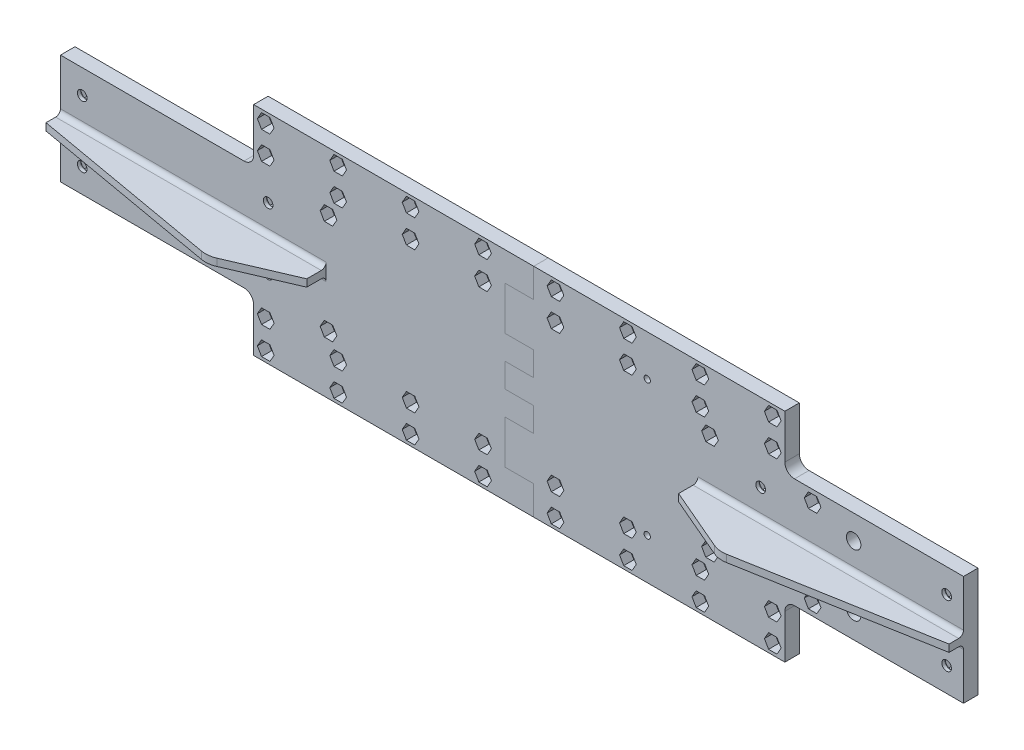
SolidWorks part; units mm, degrees
ref_plane "Top Plane" through (0, 0, 0) normal (0, 0, 1) x (1, 0, 0)
ref_plane "Right Plane" through (0, 0, 0) normal (0, 1, 0) x (1, 0, 0)
ref_plane "Front Plane" through (0, 0, 0) normal (1, 0, 0) x (0, 0, -1)
sketch "Sketch1" plane through (0, 0, 0) normal (0, 0, 1) x (1, 0, 0)
  line L0 (-187, 81) -> (187, -81) construction
  line L1 (-187, 81) -> (187, 81) construction
  line L2 (-187, 81) -> (-187, -81) construction
  line L3 (-187, -81) -> (187, -81) construction
  line L4 (187, 81) -> (187, -81) construction
  line L5 (-187, -22.75) -> (-107, -22.75) construction
  line L6 (-107, -22.75) -> (-107, -81) construction
  line L7 (113, -81) -> (113, -22.75) construction
  line L8 (113, -22.75) -> (187, -22.75) construction
  line L9 (-187, 0) -> (187, 0) construction
  line L10 (113, 22.75) -> (187, 22.75) construction
  line L11 (113, 81) -> (113, 22.75) construction
  line L12 (-107, 22.75) -> (-107, 81) construction
  line L13 (-187, 22.75) -> (-107, 22.75) construction
  line L14 (85.2, -81) -> (85.2, 81) construction
  line L15 (-93, -81) -> (-93, 81) construction
  line L16 (-187, -2.75) -> (187, -2.75) construction
  line L17 (187, 2.75) -> (-187, 2.75) construction
  text T0 "FRONT" font "Century Gothic" height in points 80
  dimension "D1" = 374
  dimension "D2" = 162
  dimension "D3" = 45.5
  dimension "D4" = 80
  dimension "D5" = 74
  dimension "D6" = 27.8
  dimension "D7" = 14
  dimension "D8" = 20
  dimension "D9" = 20
sketch "Sketch2" plane through (0, 0, 0) normal (0, 0, 1) x (1, 0, 0)
  line L0 (-187, 81) -> (-187, -81) construction
  line L1 (-187, 81) -> (187, 81) construction
  line L2 (187, 81) -> (187, -81) construction
  line L3 (-187, -81) -> (187, -81) construction
  line L4 (113, -81) -> (113, -22.75) construction
  line L5 (113, -22.75) -> (187, -22.75) construction
  line L6 (113, 22.75) -> (187, 22.75) construction
  line L7 (113, 81) -> (113, 22.75) construction
  line L8 (-107, 22.75) -> (-107, 81) construction
  line L9 (-187, 22.75) -> (-107, 22.75) construction
  line L10 (-107, -22.75) -> (-107, -81) construction
  line L11 (-187, -22.75) -> (-107, -22.75) construction
  line L12 (-187, 22.75) -> (-187, -22.75)
  line L13 (-107, 81) -> (113, 81)
  line L14 (187, 22.75) -> (187, -22.75)
  line L15 (-107, -81) -> (113, -81)
  line L16 (113, -81) -> (113, -22.75)
  line L17 (113, -22.75) -> (187, -22.75)
  line L18 (113, 22.75) -> (187, 22.75)
  line L19 (113, 81) -> (113, 22.75)
  line L20 (-107, 22.75) -> (-107, 81)
  line L21 (-187, 22.75) -> (-107, 22.75)
  line L22 (-107, -22.75) -> (-107, -81)
  line L23 (-187, -22.75) -> (-107, -22.75)
extrude "Boss-Extrude1" add sketch "Sketch2" along normal mid plane 6
sketch "Sketch5" plane through (0, 0, -3) normal (0, 0, -1) x (-1, 0, 0)
  line L0 (0, 81) -> (0, -81) construction
  line L1 (187, 81) -> (-187, 81) construction
  line L2 (187, -81) -> (-187, -81) construction
  line L4 (-180, 0) -> (178, 0) construction
  line L5 (-180, 12.75) -> (-103, 12.75) construction
  line L6 (-180, 12.75) -> (-180, -12.75) construction
  line L7 (-180, -12.75) -> (-103, -12.75) construction
  line L8 (-103, 12.75) -> (-103, -12.75) construction
  line L9 (101, 12.75) -> (178, 12.75) construction
  line L10 (101, 12.75) -> (101, -12.75) construction
  line L11 (101, -12.75) -> (178, -12.75) construction
  line L12 (178, 12.75) -> (178, -12.75) construction
  circle A8 centre (-103, -12.75) radius 2
  circle A9 centre (-103, 12.75) radius 2
  circle A10 centre (-180, 12.75) radius 2
  circle A11 centre (-180, -12.75) radius 2
  circle A12 centre (178, 12.75) radius 2
  circle A13 centre (178, -12.75) radius 2
  circle A14 centre (101, -12.75) radius 2
  circle A15 centre (101, 12.75) radius 2
  dimension "D3" = 25.5
  dimension "D6" = 4
  dimension "D1" = 77
  dimension "D2" = 103
  dimension "D4" = 101
  dimension "D5" = 77
extrude "Cut-Extrude2" cut sketch "Sketch5" against normal up to next
sketch "Sketch9" plane through (0, 0, 3) normal (0, 0, 1) x (1, 0, 0)
  line L0 (-107.9535, -35) -> (101.269, -35) construction
  line L1 (-12, -40.75) -> (18, -40.75) construction
  line L2 (-12, -29.25) -> (-42, -29.25) construction
  line L3 (-12, -29.25) -> (18, -29.25) construction
  line L4 (-194.5845, 0) -> (205.1662, 0) construction
  line L5 (3, -85.4344) -> (3, 85.4344) construction
  line L6 (-12, -40.75) -> (-42, -40.75) construction
  line L7 (-107, 81) -> (113, -81) construction
  line L8 (-40.2679, -37.75) -> (-43.7321, -37.75) construction
  line L9 (-13.7321, -37.75) -> (-15.4641, -40.75) construction
  line L10 (-15.4641, -40.75) -> (-13.7321, -43.75) construction
  line L11 (-13.7321, -43.75) -> (-10.2679, -43.75) construction
  line L12 (-10.2679, -43.75) -> (-8.5359, -40.75) construction
  line L13 (-8.5359, -40.75) -> (-10.2679, -37.75) construction
  line L14 (-10.2679, -37.75) -> (-13.7321, -37.75) construction
  line L15 (-43.7321, -37.75) -> (-45.4641, -40.75) construction
  line L16 (-45.4641, -40.75) -> (-43.7321, -43.75) construction
  line L17 (-43.7321, -43.75) -> (-40.2679, -43.75) construction
  line L18 (-40.2679, -43.75) -> (-38.5359, -40.75) construction
  line L19 (-38.5359, -40.75) -> (-40.2679, -37.75) construction
  line L20 (-70.2679, -37.75) -> (-73.7321, -37.75) construction
  line L21 (-73.7321, -37.75) -> (-75.4641, -40.75) construction
  line L22 (-75.4641, -40.75) -> (-73.7321, -43.75) construction
  line L23 (-73.7321, -43.75) -> (-70.2679, -43.75) construction
  line L24 (-70.2679, -43.75) -> (-68.5359, -40.75) construction
  line L25 (-68.5359, -40.75) -> (-70.2679, -37.75) construction
  line L26 (-100.2679, -37.75) -> (-103.7321, -37.75) construction
  line L27 (-103.7321, -37.75) -> (-105.4641, -40.75) construction
  line L28 (-105.4641, -40.75) -> (-103.7321, -43.75) construction
  line L29 (-103.7321, -43.75) -> (-100.2679, -43.75) construction
  line L30 (-100.2679, -43.75) -> (-98.5359, -40.75) construction
  line L31 (-98.5359, -40.75) -> (-100.2679, -37.75) construction
  line L32 (-43.7321, -37.75) -> (-40.2679, -43.75) construction
  line L33 (-42, -40.75) -> (-12, -40.75) construction
  line L34 (-8.5359, -29.25) -> (-10.2679, -32.25) construction
  line L35 (-10.2679, -26.25) -> (-8.5359, -29.25) construction
  line L36 (-13.7321, -26.25) -> (-10.2679, -26.25) construction
  line L37 (-15.4641, -29.25) -> (-13.7321, -26.25) construction
  line L38 (-13.7321, -32.25) -> (-15.4641, -29.25) construction
  line L39 (-10.2679, -32.25) -> (-13.7321, -32.25) construction
  line L40 (-43.7321, -26.25) -> (-40.2679, -26.25) construction
  line L41 (-45.4641, -29.25) -> (-43.7321, -26.25) construction
  line L42 (-43.7321, -32.25) -> (-45.4641, -29.25) construction
  line L43 (-40.2679, -32.25) -> (-43.7321, -32.25) construction
  line L44 (-38.5359, -29.25) -> (-40.2679, -32.25) construction
  line L45 (-40.2679, -26.25) -> (-38.5359, -29.25) construction
  line L46 (-73.7321, -26.25) -> (-70.2679, -26.25) construction
  line L47 (-75.4641, -29.25) -> (-73.7321, -26.25) construction
  line L48 (-73.7321, -32.25) -> (-75.4641, -29.25) construction
  line L49 (-70.2679, -32.25) -> (-73.7321, -32.25) construction
  line L50 (-68.5359, -29.25) -> (-70.2679, -32.25) construction
  line L51 (-70.2679, -26.25) -> (-68.5359, -29.25) construction
  line L52 (-103.7321, -26.25) -> (-100.2679, -26.25) construction
  line L53 (-105.4641, -29.25) -> (-103.7321, -26.25) construction
  line L54 (-103.7321, -32.25) -> (-105.4641, -29.25) construction
  line L55 (-100.2679, -32.25) -> (-103.7321, -32.25) construction
  line L56 (-98.5359, -29.25) -> (-100.2679, -32.25) construction
  line L57 (-100.2679, -26.25) -> (-98.5359, -29.25) construction
  line L58 (106.2679, -26.25) -> (104.5359, -29.25) construction
  line L59 (104.5359, -29.25) -> (106.2679, -32.25) construction
  line L60 (106.2679, -32.25) -> (109.7321, -32.25) construction
  line L61 (109.7321, -32.25) -> (111.4641, -29.25) construction
  line L62 (111.4641, -29.25) -> (109.7321, -26.25) construction
  line L63 (109.7321, -26.25) -> (106.2679, -26.25) construction
  line L64 (76.2679, -26.25) -> (74.5359, -29.25) construction
  line L65 (74.5359, -29.25) -> (76.2679, -32.25) construction
  line L66 (76.2679, -32.25) -> (79.7321, -32.25) construction
  line L67 (79.7321, -32.25) -> (81.4641, -29.25) construction
  line L68 (81.4641, -29.25) -> (79.7321, -26.25) construction
  line L69 (79.7321, -26.25) -> (76.2679, -26.25) construction
  line L70 (46.2679, -26.25) -> (44.5359, -29.25) construction
  line L71 (44.5359, -29.25) -> (46.2679, -32.25) construction
  line L72 (46.2679, -32.25) -> (49.7321, -32.25) construction
  line L73 (49.7321, -32.25) -> (51.4641, -29.25) construction
  line L74 (51.4641, -29.25) -> (49.7321, -26.25) construction
  line L75 (49.7321, -26.25) -> (46.2679, -26.25) construction
  line L76 (16.2679, -32.25) -> (19.7321, -32.25) construction
  line L77 (19.7321, -32.25) -> (21.4641, -29.25) construction
  line L78 (21.4641, -29.25) -> (19.7321, -26.25) construction
  line L79 (19.7321, -26.25) -> (16.2679, -26.25) construction
  line L80 (16.2679, -26.25) -> (14.5359, -29.25) construction
  line L81 (14.5359, -29.25) -> (16.2679, -32.25) construction
  line L82 (48, -40.75) -> (18, -40.75) construction
  line L83 (49.7321, -37.75) -> (46.2679, -43.75) construction
  line L84 (104.5359, -40.75) -> (106.2679, -37.75) construction
  line L85 (106.2679, -43.75) -> (104.5359, -40.75) construction
  line L86 (109.7321, -43.75) -> (106.2679, -43.75) construction
  line L87 (111.4641, -40.75) -> (109.7321, -43.75) construction
  line L88 (109.7321, -37.75) -> (111.4641, -40.75) construction
  line L89 (106.2679, -37.75) -> (109.7321, -37.75) construction
  line L90 (74.5359, -40.75) -> (76.2679, -37.75) construction
  line L91 (76.2679, -43.75) -> (74.5359, -40.75) construction
  line L92 (79.7321, -43.75) -> (76.2679, -43.75) construction
  line L93 (81.4641, -40.75) -> (79.7321, -43.75) construction
  line L94 (79.7321, -37.75) -> (81.4641, -40.75) construction
  line L95 (76.2679, -37.75) -> (79.7321, -37.75) construction
  line L96 (44.5359, -40.75) -> (46.2679, -37.75) construction
  line L97 (46.2679, -43.75) -> (44.5359, -40.75) construction
  line L98 (49.7321, -43.75) -> (46.2679, -43.75) construction
  line L99 (51.4641, -40.75) -> (49.7321, -43.75) construction
  line L100 (49.7321, -37.75) -> (51.4641, -40.75) construction
  line L101 (16.2679, -37.75) -> (19.7321, -37.75) construction
  line L102 (14.5359, -40.75) -> (16.2679, -37.75) construction
  line L103 (16.2679, -43.75) -> (14.5359, -40.75) construction
  line L104 (19.7321, -43.75) -> (16.2679, -43.75) construction
  line L105 (21.4641, -40.75) -> (19.7321, -43.75) construction
  line L106 (19.7321, -37.75) -> (21.4641, -40.75) construction
  line L107 (46.2679, -37.75) -> (49.7321, -37.75) construction
  line L108 (46.2679, 37.75) -> (49.7321, 37.75) construction
  line L109 (19.7321, 37.75) -> (21.4641, 40.75) construction
  line L110 (21.4641, 40.75) -> (19.7321, 43.75) construction
  line L111 (19.7321, 43.75) -> (16.2679, 43.75) construction
  line L112 (16.2679, 43.75) -> (14.5359, 40.75) construction
  line L113 (14.5359, 40.75) -> (16.2679, 37.75) construction
  line L114 (16.2679, 37.75) -> (19.7321, 37.75) construction
  line L115 (49.7321, 37.75) -> (51.4641, 40.75) construction
  line L116 (51.4641, 40.75) -> (49.7321, 43.75) construction
  line L117 (49.7321, 43.75) -> (46.2679, 43.75) construction
  line L118 (46.2679, 43.75) -> (44.5359, 40.75) construction
  line L119 (44.5359, 40.75) -> (46.2679, 37.75) construction
  line L120 (76.2679, 37.75) -> (79.7321, 37.75) construction
  line L121 (79.7321, 37.75) -> (81.4641, 40.75) construction
  line L122 (81.4641, 40.75) -> (79.7321, 43.75) construction
  line L123 (79.7321, 43.75) -> (76.2679, 43.75) construction
  line L124 (76.2679, 43.75) -> (74.5359, 40.75) construction
  line L125 (74.5359, 40.75) -> (76.2679, 37.75) construction
  line L126 (106.2679, 37.75) -> (109.7321, 37.75) construction
  line L127 (109.7321, 37.75) -> (111.4641, 40.75) construction
  line L128 (111.4641, 40.75) -> (109.7321, 43.75) construction
  line L129 (109.7321, 43.75) -> (106.2679, 43.75) construction
  line L130 (106.2679, 43.75) -> (104.5359, 40.75) construction
  line L131 (104.5359, 40.75) -> (106.2679, 37.75) construction
  line L132 (49.7321, 37.75) -> (46.2679, 43.75) construction
  line L133 (48, 40.75) -> (18, 40.75) construction
  line L134 (14.5359, 29.25) -> (16.2679, 32.25) construction
  line L135 (16.2679, 26.25) -> (14.5359, 29.25) construction
  line L136 (19.7321, 26.25) -> (16.2679, 26.25) construction
  line L137 (21.4641, 29.25) -> (19.7321, 26.25) construction
  line L138 (19.7321, 32.25) -> (21.4641, 29.25) construction
  line L139 (16.2679, 32.25) -> (19.7321, 32.25) construction
  line L140 (49.7321, 26.25) -> (46.2679, 26.25) construction
  line L141 (51.4641, 29.25) -> (49.7321, 26.25) construction
  line L142 (49.7321, 32.25) -> (51.4641, 29.25) construction
  line L143 (46.2679, 32.25) -> (49.7321, 32.25) construction
  line L144 (44.5359, 29.25) -> (46.2679, 32.25) construction
  line L145 (46.2679, 26.25) -> (44.5359, 29.25) construction
  line L146 (79.7321, 26.25) -> (76.2679, 26.25) construction
  line L147 (81.4641, 29.25) -> (79.7321, 26.25) construction
  line L148 (79.7321, 32.25) -> (81.4641, 29.25) construction
  line L149 (76.2679, 32.25) -> (79.7321, 32.25) construction
  line L150 (74.5359, 29.25) -> (76.2679, 32.25) construction
  line L151 (76.2679, 26.25) -> (74.5359, 29.25) construction
  line L152 (109.7321, 26.25) -> (106.2679, 26.25) construction
  line L153 (111.4641, 29.25) -> (109.7321, 26.25) construction
  line L154 (109.7321, 32.25) -> (111.4641, 29.25) construction
  line L155 (106.2679, 32.25) -> (109.7321, 32.25) construction
  line L156 (104.5359, 29.25) -> (106.2679, 32.25) construction
  line L157 (106.2679, 26.25) -> (104.5359, 29.25) construction
  line L158 (-100.2679, 26.25) -> (-98.5359, 29.25) construction
  line L159 (-98.5359, 29.25) -> (-100.2679, 32.25) construction
  line L160 (-100.2679, 32.25) -> (-103.7321, 32.25) construction
  line L161 (-103.7321, 32.25) -> (-105.4641, 29.25) construction
  line L162 (-105.4641, 29.25) -> (-103.7321, 26.25) construction
  line L163 (-103.7321, 26.25) -> (-100.2679, 26.25) construction
  line L164 (-70.2679, 26.25) -> (-68.5359, 29.25) construction
  line L165 (-68.5359, 29.25) -> (-70.2679, 32.25) construction
  line L166 (-70.2679, 32.25) -> (-73.7321, 32.25) construction
  line L167 (-73.7321, 32.25) -> (-75.4641, 29.25) construction
  line L168 (-75.4641, 29.25) -> (-73.7321, 26.25) construction
  line L169 (-73.7321, 26.25) -> (-70.2679, 26.25) construction
  line L170 (-40.2679, 26.25) -> (-38.5359, 29.25) construction
  line L171 (-38.5359, 29.25) -> (-40.2679, 32.25) construction
  line L172 (-40.2679, 32.25) -> (-43.7321, 32.25) construction
  line L173 (-43.7321, 32.25) -> (-45.4641, 29.25) construction
  line L174 (-45.4641, 29.25) -> (-43.7321, 26.25) construction
  line L175 (-43.7321, 26.25) -> (-40.2679, 26.25) construction
  line L176 (-10.2679, 32.25) -> (-13.7321, 32.25) construction
  line L177 (-13.7321, 32.25) -> (-15.4641, 29.25) construction
  line L178 (-15.4641, 29.25) -> (-13.7321, 26.25) construction
  line L179 (-13.7321, 26.25) -> (-10.2679, 26.25) construction
  line L180 (-10.2679, 26.25) -> (-8.5359, 29.25) construction
  line L181 (-8.5359, 29.25) -> (-10.2679, 32.25) construction
  line L182 (-42, 40.75) -> (-12, 40.75) construction
  line L183 (-43.7321, 37.75) -> (-40.2679, 43.75) construction
  line L184 (-98.5359, 40.75) -> (-100.2679, 37.75) construction
  line L185 (-100.2679, 43.75) -> (-98.5359, 40.75) construction
  line L186 (-103.7321, 43.75) -> (-100.2679, 43.75) construction
  line L187 (-105.4641, 40.75) -> (-103.7321, 43.75) construction
  line L188 (-103.7321, 37.75) -> (-105.4641, 40.75) construction
  line L189 (-100.2679, 37.75) -> (-103.7321, 37.75) construction
  line L190 (-68.5359, 40.75) -> (-70.2679, 37.75) construction
  line L191 (-70.2679, 43.75) -> (-68.5359, 40.75) construction
  line L192 (-73.7321, 43.75) -> (-70.2679, 43.75) construction
  line L193 (-75.4641, 40.75) -> (-73.7321, 43.75) construction
  line L194 (-73.7321, 37.75) -> (-75.4641, 40.75) construction
  line L195 (-70.2679, 37.75) -> (-73.7321, 37.75) construction
  line L196 (-38.5359, 40.75) -> (-40.2679, 37.75) construction
  line L197 (-40.2679, 43.75) -> (-38.5359, 40.75) construction
  line L198 (-43.7321, 43.75) -> (-40.2679, 43.75) construction
  line L199 (-45.4641, 40.75) -> (-43.7321, 43.75) construction
  line L200 (-43.7321, 37.75) -> (-45.4641, 40.75) construction
  line L201 (-10.2679, 37.75) -> (-13.7321, 37.75) construction
  line L202 (-8.5359, 40.75) -> (-10.2679, 37.75) construction
  line L203 (-10.2679, 43.75) -> (-8.5359, 40.75) construction
  line L204 (-13.7321, 43.75) -> (-10.2679, 43.75) construction
  line L205 (-15.4641, 40.75) -> (-13.7321, 43.75) construction
  line L206 (-13.7321, 37.75) -> (-15.4641, 40.75) construction
  line L207 (-40.2679, 37.75) -> (-43.7321, 37.75) construction
  line L208 (-12, 40.75) -> (-42, 40.75) construction
  line L209 (-12, 29.25) -> (18, 29.25) construction
  line L210 (-12, 29.25) -> (-42, 29.25) construction
  line L211 (-12, 40.75) -> (18, 40.75) construction
  line L212 (-107.9535, 35) -> (101.269, 35) construction
  circle A0 centre (-12, -40.75) radius 1.75
  circle A1 centre (-42, -40.75) radius 1.75
  circle A2 centre (-72, -40.75) radius 1.75
  circle A3 centre (-102, -40.75) radius 1.75
  circle A4 centre (108, -40.75) radius 1.75
  circle A5 centre (78, -40.75) radius 1.75
  circle A6 centre (48, -40.75) radius 1.75
  circle A7 centre (18, -40.75) radius 1.75
  circle A8 centre (18, -29.25) radius 1.75
  circle A9 centre (48, -29.25) radius 1.75
  circle A10 centre (78, -29.25) radius 1.75
  circle A11 centre (108, -29.25) radius 1.75
  circle A12 centre (-102, -29.25) radius 1.75
  circle A13 centre (-72, -29.25) radius 1.75
  circle A14 centre (-42, -29.25) radius 1.75
  circle A15 centre (-12, -29.25) radius 1.75
  circle A16 centre (-12, -40.75) radius 3 construction
  circle A17 centre (-12, 40.75) radius 3 construction
  circle A18 centre (-12, 29.25) radius 1.75
  circle A19 centre (-42, 29.25) radius 1.75
  circle A20 centre (-72, 29.25) radius 1.75
  circle A21 centre (-102, 29.25) radius 1.75
  circle A22 centre (108, 29.25) radius 1.75
  circle A23 centre (78, 29.25) radius 1.75
  circle A24 centre (48, 29.25) radius 1.75
  circle A25 centre (18, 29.25) radius 1.75
  circle A26 centre (18, 40.75) radius 1.75
  circle A27 centre (48, 40.75) radius 1.75
  circle A28 centre (78, 40.75) radius 1.75
  circle A29 centre (108, 40.75) radius 1.75
  circle A30 centre (-102, 40.75) radius 1.75
  circle A31 centre (-72, 40.75) radius 1.75
  circle A32 centre (-42, 40.75) radius 1.75
  circle A33 centre (-12, 40.75) radius 1.75
  point P6 (3, -40.75)
  point P39 (3, -29.25)
  point P46 (3, 0)
  point P277 (3, 29.25)
  point P278 (3, 40.75)
  dimension "D3" = 3.5
  dimension "D1" = 11.5
  dimension "D2" = 35
  dimension "D5" = 30
  dimension "D6" = 6
  dimension "D4" = 4
  dimension "D7" = 4
extrude "Cut-Extrude6" cut sketch "Sketch9" against normal through all
sketch "Sketch10" plane through (0, 0, 3) normal (0, 0, 1) x (1, 0, 0)
  line L0 (-103.7321, -43.75) -> (-100.2679, -43.75) construction
  line L1 (-105.4641, -40.75) -> (-103.7321, -43.75) construction
  line L2 (-103.7321, -37.75) -> (-105.4641, -40.75) construction
  line L3 (-100.2679, -37.75) -> (-103.7321, -37.75) construction
  line L4 (-98.5359, -40.75) -> (-100.2679, -37.75) construction
  line L5 (-100.2679, -43.75) -> (-98.5359, -40.75) construction
  line L6 (-103.7321, -43.75) -> (-100.2679, -43.75)
  line L7 (-105.4641, -40.75) -> (-103.7321, -43.75)
  line L8 (-103.7321, -37.75) -> (-105.4641, -40.75)
  line L9 (-100.2679, -37.75) -> (-103.7321, -37.75)
  line L10 (-98.5359, -40.75) -> (-100.2679, -37.75)
  line L11 (-100.2679, -43.75) -> (-98.5359, -40.75)
  line L12 (-73.7321, -43.75) -> (-70.2679, -43.75) construction
  line L13 (-75.4641, -40.75) -> (-73.7321, -43.75) construction
  line L14 (-73.7321, -37.75) -> (-75.4641, -40.75) construction
  line L15 (-70.2679, -37.75) -> (-73.7321, -37.75) construction
  line L16 (-68.5359, -40.75) -> (-70.2679, -37.75) construction
  line L17 (-70.2679, -43.75) -> (-68.5359, -40.75) construction
  line L18 (-73.7321, -43.75) -> (-70.2679, -43.75)
  line L19 (-75.4641, -40.75) -> (-73.7321, -43.75)
  line L20 (-73.7321, -37.75) -> (-75.4641, -40.75)
  line L21 (-70.2679, -37.75) -> (-73.7321, -37.75)
  line L22 (-68.5359, -40.75) -> (-70.2679, -37.75)
  line L23 (-70.2679, -43.75) -> (-68.5359, -40.75)
  line L24 (-43.7321, -43.75) -> (-40.2679, -43.75) construction
  line L25 (-45.4641, -40.75) -> (-43.7321, -43.75) construction
  line L26 (-43.7321, -37.75) -> (-45.4641, -40.75) construction
  line L27 (-40.2679, -37.75) -> (-43.7321, -37.75) construction
  line L28 (-38.5359, -40.75) -> (-40.2679, -37.75) construction
  line L29 (-40.2679, -43.75) -> (-38.5359, -40.75) construction
  line L30 (-43.7321, -43.75) -> (-40.2679, -43.75)
  line L31 (-45.4641, -40.75) -> (-43.7321, -43.75)
  line L32 (-43.7321, -37.75) -> (-45.4641, -40.75)
  line L33 (-40.2679, -37.75) -> (-43.7321, -37.75)
  line L34 (-38.5359, -40.75) -> (-40.2679, -37.75)
  line L35 (-40.2679, -43.75) -> (-38.5359, -40.75)
  line L36 (-13.7321, -43.75) -> (-10.2679, -43.75) construction
  line L37 (-15.4641, -40.75) -> (-13.7321, -43.75) construction
  line L38 (-13.7321, -37.75) -> (-15.4641, -40.75) construction
  line L39 (-10.2679, -37.75) -> (-13.7321, -37.75) construction
  line L40 (-8.5359, -40.75) -> (-10.2679, -37.75) construction
  line L41 (-10.2679, -43.75) -> (-8.5359, -40.75) construction
  line L42 (-13.7321, -43.75) -> (-10.2679, -43.75)
  line L43 (-15.4641, -40.75) -> (-13.7321, -43.75)
  line L44 (-13.7321, -37.75) -> (-15.4641, -40.75)
  line L45 (-10.2679, -37.75) -> (-13.7321, -37.75)
  line L46 (-8.5359, -40.75) -> (-10.2679, -37.75)
  line L47 (-10.2679, -43.75) -> (-8.5359, -40.75)
  line L48 (79.7321, -43.75) -> (76.2679, -43.75) construction
  line L49 (81.4641, -40.75) -> (79.7321, -43.75) construction
  line L50 (79.7321, -37.75) -> (81.4641, -40.75) construction
  line L51 (76.2679, -37.75) -> (79.7321, -37.75) construction
  line L52 (74.5359, -40.75) -> (76.2679, -37.75) construction
  line L53 (76.2679, -43.75) -> (74.5359, -40.75) construction
  line L54 (46.2679, -37.75) -> (49.7321, -37.75) construction
  line L55 (44.5359, -40.75) -> (46.2679, -37.75) construction
  line L56 (46.2679, -43.75) -> (44.5359, -40.75) construction
  line L57 (16.2679, -43.75) -> (14.5359, -40.75) construction
  line L58 (19.7321, -43.75) -> (16.2679, -43.75) construction
  line L59 (21.4641, -40.75) -> (19.7321, -43.75) construction
  line L60 (19.7321, -37.75) -> (21.4641, -40.75) construction
  line L61 (16.2679, -37.75) -> (19.7321, -37.75) construction
  line L62 (14.5359, -40.75) -> (16.2679, -37.75) construction
  line L63 (79.7321, -43.75) -> (76.2679, -43.75)
  line L64 (81.4641, -40.75) -> (79.7321, -43.75)
  line L65 (79.7321, -37.75) -> (81.4641, -40.75)
  line L66 (76.2679, -37.75) -> (79.7321, -37.75)
  line L67 (74.5359, -40.75) -> (76.2679, -37.75)
  line L68 (76.2679, -43.75) -> (74.5359, -40.75)
  line L69 (46.2679, -37.75) -> (49.7321, -37.75)
  line L70 (44.5359, -40.75) -> (46.2679, -37.75)
  line L71 (46.2679, -43.75) -> (44.5359, -40.75)
  line L72 (16.2679, -43.75) -> (14.5359, -40.75)
  line L73 (19.7321, -43.75) -> (16.2679, -43.75)
  line L74 (21.4641, -40.75) -> (19.7321, -43.75)
  line L75 (19.7321, -37.75) -> (21.4641, -40.75)
  line L76 (16.2679, -37.75) -> (19.7321, -37.75)
  line L77 (14.5359, -40.75) -> (16.2679, -37.75)
  line L78 (49.7321, -43.75) -> (46.2679, -43.75) construction
  line L79 (51.4641, -40.75) -> (49.7321, -43.75) construction
  line L80 (49.7321, -37.75) -> (51.4641, -40.75) construction
  line L81 (49.7321, -43.75) -> (46.2679, -43.75)
  line L82 (51.4641, -40.75) -> (49.7321, -43.75)
  line L83 (49.7321, -37.75) -> (51.4641, -40.75)
  line L84 (46.2679, -32.25) -> (49.7321, -32.25) construction
  line L85 (44.5359, -29.25) -> (46.2679, -32.25) construction
  line L86 (46.2679, -26.25) -> (44.5359, -29.25) construction
  line L87 (49.7321, -26.25) -> (46.2679, -26.25) construction
  line L88 (51.4641, -29.25) -> (49.7321, -26.25) construction
  line L89 (49.7321, -32.25) -> (51.4641, -29.25) construction
  line L90 (79.7321, -32.25) -> (81.4641, -29.25) construction
  line L91 (76.2679, -32.25) -> (79.7321, -32.25) construction
  line L92 (74.5359, -29.25) -> (76.2679, -32.25) construction
  line L93 (76.2679, -26.25) -> (74.5359, -29.25) construction
  line L94 (79.7321, -26.25) -> (76.2679, -26.25) construction
  line L95 (81.4641, -29.25) -> (79.7321, -26.25) construction
  line L96 (106.2679, -26.25) -> (104.5359, -29.25) construction
  line L97 (109.7321, -26.25) -> (106.2679, -26.25) construction
  line L98 (111.4641, -29.25) -> (109.7321, -26.25) construction
  line L99 (109.7321, -32.25) -> (111.4641, -29.25) construction
  line L100 (106.2679, -32.25) -> (109.7321, -32.25) construction
  line L101 (104.5359, -29.25) -> (106.2679, -32.25) construction
  line L102 (106.2679, -43.75) -> (104.5359, -40.75) construction
  line L103 (109.7321, -43.75) -> (106.2679, -43.75) construction
  line L104 (111.4641, -40.75) -> (109.7321, -43.75) construction
  line L105 (109.7321, -37.75) -> (111.4641, -40.75) construction
  line L106 (106.2679, -37.75) -> (109.7321, -37.75) construction
  line L107 (104.5359, -40.75) -> (106.2679, -37.75) construction
  line L108 (46.2679, -32.25) -> (49.7321, -32.25)
  line L109 (44.5359, -29.25) -> (46.2679, -32.25)
  line L110 (46.2679, -26.25) -> (44.5359, -29.25)
  line L111 (49.7321, -26.25) -> (46.2679, -26.25)
  line L112 (51.4641, -29.25) -> (49.7321, -26.25)
  line L113 (49.7321, -32.25) -> (51.4641, -29.25)
  line L114 (79.7321, -32.25) -> (81.4641, -29.25)
  line L115 (76.2679, -32.25) -> (79.7321, -32.25)
  line L116 (74.5359, -29.25) -> (76.2679, -32.25)
  line L117 (76.2679, -26.25) -> (74.5359, -29.25)
  line L118 (79.7321, -26.25) -> (76.2679, -26.25)
  line L119 (81.4641, -29.25) -> (79.7321, -26.25)
  line L120 (106.2679, -26.25) -> (104.5359, -29.25)
  line L121 (109.7321, -26.25) -> (106.2679, -26.25)
  line L122 (111.4641, -29.25) -> (109.7321, -26.25)
  line L123 (109.7321, -32.25) -> (111.4641, -29.25)
  line L124 (106.2679, -32.25) -> (109.7321, -32.25)
  line L125 (104.5359, -29.25) -> (106.2679, -32.25)
  line L126 (106.2679, -43.75) -> (104.5359, -40.75)
  line L127 (109.7321, -43.75) -> (106.2679, -43.75)
  line L128 (111.4641, -40.75) -> (109.7321, -43.75)
  line L129 (109.7321, -37.75) -> (111.4641, -40.75)
  line L130 (106.2679, -37.75) -> (109.7321, -37.75)
  line L131 (104.5359, -40.75) -> (106.2679, -37.75)
  line L132 (-43.7321, -32.25) -> (-45.4641, -29.25) construction
  line L133 (-40.2679, -32.25) -> (-43.7321, -32.25) construction
  line L134 (-38.5359, -29.25) -> (-40.2679, -32.25) construction
  line L135 (-40.2679, -26.25) -> (-38.5359, -29.25) construction
  line L136 (-43.7321, -26.25) -> (-40.2679, -26.25) construction
  line L137 (-45.4641, -29.25) -> (-43.7321, -26.25) construction
  line L138 (-13.7321, -32.25) -> (-15.4641, -29.25) construction
  line L139 (-10.2679, -32.25) -> (-13.7321, -32.25) construction
  line L140 (-8.5359, -29.25) -> (-10.2679, -32.25) construction
  line L141 (-10.2679, -26.25) -> (-8.5359, -29.25) construction
  line L142 (-13.7321, -26.25) -> (-10.2679, -26.25) construction
  line L143 (-15.4641, -29.25) -> (-13.7321, -26.25) construction
  line L144 (19.7321, -32.25) -> (21.4641, -29.25) construction
  line L145 (16.2679, -32.25) -> (19.7321, -32.25) construction
  line L146 (14.5359, -29.25) -> (16.2679, -32.25) construction
  line L147 (16.2679, -26.25) -> (14.5359, -29.25) construction
  line L148 (19.7321, -26.25) -> (16.2679, -26.25) construction
  line L149 (21.4641, -29.25) -> (19.7321, -26.25) construction
  line L150 (-43.7321, -32.25) -> (-45.4641, -29.25)
  line L151 (-40.2679, -32.25) -> (-43.7321, -32.25)
  line L152 (-38.5359, -29.25) -> (-40.2679, -32.25)
  line L153 (-40.2679, -26.25) -> (-38.5359, -29.25)
  line L154 (-43.7321, -26.25) -> (-40.2679, -26.25)
  line L155 (-45.4641, -29.25) -> (-43.7321, -26.25)
  line L156 (-13.7321, -32.25) -> (-15.4641, -29.25)
  line L157 (-10.2679, -32.25) -> (-13.7321, -32.25)
  line L158 (-8.5359, -29.25) -> (-10.2679, -32.25)
  line L159 (-10.2679, -26.25) -> (-8.5359, -29.25)
  line L160 (-13.7321, -26.25) -> (-10.2679, -26.25)
  line L161 (-15.4641, -29.25) -> (-13.7321, -26.25)
  line L162 (19.7321, -32.25) -> (21.4641, -29.25)
  line L163 (16.2679, -32.25) -> (19.7321, -32.25)
  line L164 (14.5359, -29.25) -> (16.2679, -32.25)
  line L165 (16.2679, -26.25) -> (14.5359, -29.25)
  line L166 (19.7321, -26.25) -> (16.2679, -26.25)
  line L167 (21.4641, -29.25) -> (19.7321, -26.25)
  line L168 (-100.2679, -32.25) -> (-103.7321, -32.25) construction
  line L169 (-98.5359, -29.25) -> (-100.2679, -32.25) construction
  line L170 (-100.2679, -26.25) -> (-98.5359, -29.25) construction
  line L171 (-103.7321, -26.25) -> (-100.2679, -26.25) construction
  line L172 (-105.4641, -29.25) -> (-103.7321, -26.25) construction
  line L173 (-103.7321, -32.25) -> (-105.4641, -29.25) construction
  line L174 (-68.5359, -29.25) -> (-70.2679, -32.25) construction
  line L175 (-70.2679, -26.25) -> (-68.5359, -29.25) construction
  line L176 (-73.7321, -26.25) -> (-70.2679, -26.25) construction
  line L177 (-75.4641, -29.25) -> (-73.7321, -26.25) construction
  line L178 (-73.7321, -32.25) -> (-75.4641, -29.25) construction
  line L179 (-70.2679, -32.25) -> (-73.7321, -32.25) construction
  line L180 (-100.2679, -32.25) -> (-103.7321, -32.25)
  line L181 (-98.5359, -29.25) -> (-100.2679, -32.25)
  line L182 (-100.2679, -26.25) -> (-98.5359, -29.25)
  line L183 (-103.7321, -26.25) -> (-100.2679, -26.25)
  line L184 (-105.4641, -29.25) -> (-103.7321, -26.25)
  line L185 (-103.7321, -32.25) -> (-105.4641, -29.25)
  line L186 (-68.5359, -29.25) -> (-70.2679, -32.25)
  line L187 (-70.2679, -26.25) -> (-68.5359, -29.25)
  line L188 (-73.7321, -26.25) -> (-70.2679, -26.25)
  line L189 (-75.4641, -29.25) -> (-73.7321, -26.25)
  line L190 (-73.7321, -32.25) -> (-75.4641, -29.25)
  line L191 (-70.2679, -32.25) -> (-73.7321, -32.25)
  line L192 (-73.7321, 26.25) -> (-70.2679, 26.25) construction
  line L193 (-75.4641, 29.25) -> (-73.7321, 26.25) construction
  line L194 (-73.7321, 32.25) -> (-75.4641, 29.25) construction
  line L195 (-70.2679, 32.25) -> (-73.7321, 32.25) construction
  line L196 (-68.5359, 29.25) -> (-70.2679, 32.25) construction
  line L197 (-70.2679, 26.25) -> (-68.5359, 29.25) construction
  line L198 (-73.7321, 37.75) -> (-75.4641, 40.75) construction
  line L199 (-70.2679, 37.75) -> (-73.7321, 37.75) construction
  line L200 (-68.5359, 40.75) -> (-70.2679, 37.75) construction
  line L201 (-70.2679, 43.75) -> (-68.5359, 40.75) construction
  line L202 (-73.7321, 43.75) -> (-70.2679, 43.75) construction
  line L203 (-75.4641, 40.75) -> (-73.7321, 43.75) construction
  line L204 (-103.7321, 26.25) -> (-100.2679, 26.25) construction
  line L205 (-105.4641, 29.25) -> (-103.7321, 26.25) construction
  line L206 (-103.7321, 32.25) -> (-105.4641, 29.25) construction
  line L207 (-100.2679, 32.25) -> (-103.7321, 32.25) construction
  line L208 (-98.5359, 29.25) -> (-100.2679, 32.25) construction
  line L209 (-100.2679, 26.25) -> (-98.5359, 29.25) construction
  line L210 (-103.7321, 37.75) -> (-105.4641, 40.75) construction
  line L211 (-100.2679, 37.75) -> (-103.7321, 37.75) construction
  line L212 (-98.5359, 40.75) -> (-100.2679, 37.75) construction
  line L213 (-100.2679, 43.75) -> (-98.5359, 40.75) construction
  line L214 (-103.7321, 43.75) -> (-100.2679, 43.75) construction
  line L215 (-105.4641, 40.75) -> (-103.7321, 43.75) construction
  line L216 (-73.7321, 26.25) -> (-70.2679, 26.25)
  line L217 (-75.4641, 29.25) -> (-73.7321, 26.25)
  line L218 (-73.7321, 32.25) -> (-75.4641, 29.25)
  line L219 (-70.2679, 32.25) -> (-73.7321, 32.25)
  line L220 (-68.5359, 29.25) -> (-70.2679, 32.25)
  line L221 (-70.2679, 26.25) -> (-68.5359, 29.25)
  line L222 (-73.7321, 37.75) -> (-75.4641, 40.75)
  line L223 (-70.2679, 37.75) -> (-73.7321, 37.75)
  line L224 (-68.5359, 40.75) -> (-70.2679, 37.75)
  line L225 (-70.2679, 43.75) -> (-68.5359, 40.75)
  line L226 (-73.7321, 43.75) -> (-70.2679, 43.75)
  line L227 (-75.4641, 40.75) -> (-73.7321, 43.75)
  line L228 (-103.7321, 26.25) -> (-100.2679, 26.25)
  line L229 (-105.4641, 29.25) -> (-103.7321, 26.25)
  line L230 (-103.7321, 32.25) -> (-105.4641, 29.25)
  line L231 (-100.2679, 32.25) -> (-103.7321, 32.25)
  line L232 (-98.5359, 29.25) -> (-100.2679, 32.25)
  line L233 (-100.2679, 26.25) -> (-98.5359, 29.25)
  line L234 (-103.7321, 37.75) -> (-105.4641, 40.75)
  line L235 (-100.2679, 37.75) -> (-103.7321, 37.75)
  line L236 (-98.5359, 40.75) -> (-100.2679, 37.75)
  line L237 (-100.2679, 43.75) -> (-98.5359, 40.75)
  line L238 (-103.7321, 43.75) -> (-100.2679, 43.75)
  line L239 (-105.4641, 40.75) -> (-103.7321, 43.75)
  line L240 (-15.4641, 29.25) -> (-13.7321, 26.25) construction
  line L241 (-13.7321, 32.25) -> (-15.4641, 29.25) construction
  line L242 (-10.2679, 32.25) -> (-13.7321, 32.25) construction
  line L243 (-8.5359, 29.25) -> (-10.2679, 32.25) construction
  line L244 (-10.2679, 26.25) -> (-8.5359, 29.25) construction
  line L245 (-13.7321, 26.25) -> (-10.2679, 26.25) construction
  line L246 (-13.7321, 37.75) -> (-15.4641, 40.75) construction
  line L247 (-10.2679, 37.75) -> (-13.7321, 37.75) construction
  line L248 (-8.5359, 40.75) -> (-10.2679, 37.75) construction
  line L249 (-10.2679, 43.75) -> (-8.5359, 40.75) construction
  line L250 (-13.7321, 43.75) -> (-10.2679, 43.75) construction
  line L251 (-15.4641, 40.75) -> (-13.7321, 43.75) construction
  line L252 (-43.7321, 26.25) -> (-40.2679, 26.25) construction
  line L253 (-45.4641, 29.25) -> (-43.7321, 26.25) construction
  line L254 (-43.7321, 32.25) -> (-45.4641, 29.25) construction
  line L255 (-40.2679, 32.25) -> (-43.7321, 32.25) construction
  line L256 (-38.5359, 29.25) -> (-40.2679, 32.25) construction
  line L257 (-40.2679, 26.25) -> (-38.5359, 29.25) construction
  line L258 (-40.2679, 37.75) -> (-43.7321, 37.75) construction
  line L259 (-38.5359, 40.75) -> (-40.2679, 37.75) construction
  line L260 (-40.2679, 43.75) -> (-38.5359, 40.75) construction
  line L261 (-43.7321, 43.75) -> (-40.2679, 43.75) construction
  line L262 (-45.4641, 40.75) -> (-43.7321, 43.75) construction
  line L263 (-43.7321, 37.75) -> (-45.4641, 40.75) construction
  line L264 (-15.4641, 29.25) -> (-13.7321, 26.25)
  line L265 (-13.7321, 32.25) -> (-15.4641, 29.25)
  line L266 (-10.2679, 32.25) -> (-13.7321, 32.25)
  line L267 (-8.5359, 29.25) -> (-10.2679, 32.25)
  line L268 (-10.2679, 26.25) -> (-8.5359, 29.25)
  line L269 (-13.7321, 26.25) -> (-10.2679, 26.25)
  line L270 (-13.7321, 37.75) -> (-15.4641, 40.75)
  line L271 (-10.2679, 37.75) -> (-13.7321, 37.75)
  line L272 (-8.5359, 40.75) -> (-10.2679, 37.75)
  line L273 (-10.2679, 43.75) -> (-8.5359, 40.75)
  line L274 (-13.7321, 43.75) -> (-10.2679, 43.75)
  line L275 (-15.4641, 40.75) -> (-13.7321, 43.75)
  line L276 (-43.7321, 26.25) -> (-40.2679, 26.25)
  line L277 (-45.4641, 29.25) -> (-43.7321, 26.25)
  line L278 (-43.7321, 32.25) -> (-45.4641, 29.25)
  line L279 (-40.2679, 32.25) -> (-43.7321, 32.25)
  line L280 (-38.5359, 29.25) -> (-40.2679, 32.25)
  line L281 (-40.2679, 26.25) -> (-38.5359, 29.25)
  line L282 (-40.2679, 37.75) -> (-43.7321, 37.75)
  line L283 (-38.5359, 40.75) -> (-40.2679, 37.75)
  line L284 (-40.2679, 43.75) -> (-38.5359, 40.75)
  line L285 (-43.7321, 43.75) -> (-40.2679, 43.75)
  line L286 (-45.4641, 40.75) -> (-43.7321, 43.75)
  line L287 (-43.7321, 37.75) -> (-45.4641, 40.75)
  line L288 (46.2679, 26.25) -> (44.5359, 29.25) construction
  line L289 (49.7321, 26.25) -> (46.2679, 26.25) construction
  line L290 (51.4641, 29.25) -> (49.7321, 26.25) construction
  line L291 (49.7321, 32.25) -> (51.4641, 29.25) construction
  line L292 (46.2679, 32.25) -> (49.7321, 32.25) construction
  line L293 (44.5359, 29.25) -> (46.2679, 32.25) construction
  line L294 (46.2679, 37.75) -> (49.7321, 37.75) construction
  line L295 (44.5359, 40.75) -> (46.2679, 37.75) construction
  line L296 (46.2679, 43.75) -> (44.5359, 40.75) construction
  line L297 (49.7321, 43.75) -> (46.2679, 43.75) construction
  line L298 (51.4641, 40.75) -> (49.7321, 43.75) construction
  line L299 (49.7321, 37.75) -> (51.4641, 40.75) construction
  line L300 (16.2679, 26.25) -> (14.5359, 29.25) construction
  line L301 (19.7321, 26.25) -> (16.2679, 26.25) construction
  line L302 (21.4641, 29.25) -> (19.7321, 26.25) construction
  line L303 (19.7321, 32.25) -> (21.4641, 29.25) construction
  line L304 (16.2679, 32.25) -> (19.7321, 32.25) construction
  line L305 (14.5359, 29.25) -> (16.2679, 32.25) construction
  line L306 (16.2679, 37.75) -> (19.7321, 37.75) construction
  line L307 (14.5359, 40.75) -> (16.2679, 37.75) construction
  line L308 (16.2679, 43.75) -> (14.5359, 40.75) construction
  line L309 (19.7321, 43.75) -> (16.2679, 43.75) construction
  line L310 (21.4641, 40.75) -> (19.7321, 43.75) construction
  line L311 (19.7321, 37.75) -> (21.4641, 40.75) construction
  line L312 (46.2679, 26.25) -> (44.5359, 29.25)
  line L313 (49.7321, 26.25) -> (46.2679, 26.25)
  line L314 (51.4641, 29.25) -> (49.7321, 26.25)
  line L315 (49.7321, 32.25) -> (51.4641, 29.25)
  line L316 (46.2679, 32.25) -> (49.7321, 32.25)
  line L317 (44.5359, 29.25) -> (46.2679, 32.25)
  line L318 (46.2679, 37.75) -> (49.7321, 37.75)
  line L319 (44.5359, 40.75) -> (46.2679, 37.75)
  line L320 (46.2679, 43.75) -> (44.5359, 40.75)
  line L321 (49.7321, 43.75) -> (46.2679, 43.75)
  line L322 (51.4641, 40.75) -> (49.7321, 43.75)
  line L323 (49.7321, 37.75) -> (51.4641, 40.75)
  line L324 (16.2679, 26.25) -> (14.5359, 29.25)
  line L325 (19.7321, 26.25) -> (16.2679, 26.25)
  line L326 (21.4641, 29.25) -> (19.7321, 26.25)
  line L327 (19.7321, 32.25) -> (21.4641, 29.25)
  line L328 (16.2679, 32.25) -> (19.7321, 32.25)
  line L329 (14.5359, 29.25) -> (16.2679, 32.25)
  line L330 (16.2679, 37.75) -> (19.7321, 37.75)
  line L331 (14.5359, 40.75) -> (16.2679, 37.75)
  line L332 (16.2679, 43.75) -> (14.5359, 40.75)
  line L333 (19.7321, 43.75) -> (16.2679, 43.75)
  line L334 (21.4641, 40.75) -> (19.7321, 43.75)
  line L335 (19.7321, 37.75) -> (21.4641, 40.75)
  line L336 (106.2679, 26.25) -> (104.5359, 29.25) construction
  line L337 (109.7321, 26.25) -> (106.2679, 26.25) construction
  line L338 (111.4641, 29.25) -> (109.7321, 26.25) construction
  line L339 (109.7321, 32.25) -> (111.4641, 29.25) construction
  line L340 (106.2679, 32.25) -> (109.7321, 32.25) construction
  line L341 (104.5359, 29.25) -> (106.2679, 32.25) construction
  line L342 (106.2679, 37.75) -> (109.7321, 37.75) construction
  line L343 (104.5359, 40.75) -> (106.2679, 37.75) construction
  line L344 (106.2679, 43.75) -> (104.5359, 40.75) construction
  line L345 (109.7321, 43.75) -> (106.2679, 43.75) construction
  line L346 (111.4641, 40.75) -> (109.7321, 43.75) construction
  line L347 (109.7321, 37.75) -> (111.4641, 40.75) construction
  line L348 (76.2679, 26.25) -> (74.5359, 29.25) construction
  line L349 (79.7321, 26.25) -> (76.2679, 26.25) construction
  line L350 (81.4641, 29.25) -> (79.7321, 26.25) construction
  line L351 (79.7321, 32.25) -> (81.4641, 29.25) construction
  line L352 (76.2679, 32.25) -> (79.7321, 32.25) construction
  line L353 (74.5359, 29.25) -> (76.2679, 32.25) construction
  line L354 (76.2679, 37.75) -> (79.7321, 37.75) construction
  line L355 (74.5359, 40.75) -> (76.2679, 37.75) construction
  line L356 (76.2679, 43.75) -> (74.5359, 40.75) construction
  line L357 (79.7321, 43.75) -> (76.2679, 43.75) construction
  line L358 (81.4641, 40.75) -> (79.7321, 43.75) construction
  line L359 (79.7321, 37.75) -> (81.4641, 40.75) construction
  line L360 (106.2679, 26.25) -> (104.5359, 29.25)
  line L361 (109.7321, 26.25) -> (106.2679, 26.25)
  line L362 (111.4641, 29.25) -> (109.7321, 26.25)
  line L363 (109.7321, 32.25) -> (111.4641, 29.25)
  line L364 (106.2679, 32.25) -> (109.7321, 32.25)
  line L365 (104.5359, 29.25) -> (106.2679, 32.25)
  line L366 (106.2679, 37.75) -> (109.7321, 37.75)
  line L367 (104.5359, 40.75) -> (106.2679, 37.75)
  line L368 (106.2679, 43.75) -> (104.5359, 40.75)
  line L369 (109.7321, 43.75) -> (106.2679, 43.75)
  line L370 (111.4641, 40.75) -> (109.7321, 43.75)
  line L371 (109.7321, 37.75) -> (111.4641, 40.75)
  line L372 (76.2679, 26.25) -> (74.5359, 29.25)
  line L373 (79.7321, 26.25) -> (76.2679, 26.25)
  line L374 (81.4641, 29.25) -> (79.7321, 26.25)
  line L375 (79.7321, 32.25) -> (81.4641, 29.25)
  line L376 (76.2679, 32.25) -> (79.7321, 32.25)
  line L377 (74.5359, 29.25) -> (76.2679, 32.25)
  line L378 (76.2679, 37.75) -> (79.7321, 37.75)
  line L379 (74.5359, 40.75) -> (76.2679, 37.75)
  line L380 (76.2679, 43.75) -> (74.5359, 40.75)
  line L381 (79.7321, 43.75) -> (76.2679, 43.75)
  line L382 (81.4641, 40.75) -> (79.7321, 43.75)
  line L383 (79.7321, 37.75) -> (81.4641, 40.75)
extrude "Cut-Extrude7" cut sketch "Sketch10" against normal blind 4.2
sketch "Sketch13" plane through (0, 0, 3) normal (0, 0, 1) x (1, 0, 0)
  line L1 (-107, -81) -> (113, -81)
  line L2 (-107, -81) -> (-107, -45)
  line L3 (-107, -45) -> (113, -45)
  line L4 (113, -81) -> (113, -45)
  line L6 (-187, 0) -> (187, 0) construction
  line L7 (-187, 0) -> (187, 0) construction
  line L8 (113, 81) -> (113, 45)
  line L9 (-107, 45) -> (113, 45)
  line L10 (-107, 81) -> (-107, 45)
  line L11 (-107, 81) -> (113, 81)
  line L12 (113, -81) -> (113, -22.75) construction
  dimension "D1" = 90
extrude "Cut-Extrude12" cut sketch "Sketch13" against normal through all
sketch "Sketch14" plane through (0, 0, 3) normal (0, 0, 1) x (1, 0, 0)
  line L0 (-76, -20.75) -> (82, 20.75) construction
  line L1 (-76, -20.75) -> (82, -20.75) construction
  line L2 (-76, -20.75) -> (-76, 20.75) construction
  line L3 (-76, 20.75) -> (82, 20.75) construction
  line L4 (82, -20.75) -> (82, 20.75) construction
  line L5 (-107, -81) -> (113, 81) construction
  line L6 (3, 20.75) -> (3, -20.75) construction
  line L7 (-77.7321, -17.75) -> (-79.4641, -20.75) construction
  line L8 (-79.4641, -20.75) -> (-77.7321, -23.75) construction
  line L9 (-77.7321, -23.75) -> (-74.2679, -23.75) construction
  line L10 (-74.2679, -23.75) -> (-72.5359, -20.75) construction
  line L11 (-72.5359, -20.75) -> (-74.2679, -17.75) construction
  line L12 (-74.2679, -17.75) -> (-77.7321, -17.75) construction
  line L13 (-76, 0) -> (82, 0) construction
  line L14 (-74.2679, 17.75) -> (-77.7321, 17.75) construction
  line L15 (-72.5359, 20.75) -> (-74.2679, 17.75) construction
  line L16 (-74.2679, 23.75) -> (-72.5359, 20.75) construction
  line L17 (-77.7321, 23.75) -> (-74.2679, 23.75) construction
  line L18 (-79.4641, 20.75) -> (-77.7321, 23.75) construction
  line L19 (-77.7321, 17.75) -> (-79.4641, 20.75) construction
  line L20 (83.7321, 17.75) -> (85.4641, 20.75) construction
  line L21 (85.4641, 20.75) -> (83.7321, 23.75) construction
  line L22 (83.7321, 23.75) -> (80.2679, 23.75) construction
  line L23 (80.2679, 23.75) -> (78.5359, 20.75) construction
  line L24 (78.5359, 20.75) -> (80.2679, 17.75) construction
  line L25 (80.2679, 17.75) -> (83.7321, 17.75) construction
  line L26 (80.2679, -17.75) -> (83.7321, -17.75) construction
  line L27 (78.5359, -20.75) -> (80.2679, -17.75) construction
  line L28 (80.2679, -23.75) -> (78.5359, -20.75) construction
  line L29 (83.7321, -23.75) -> (80.2679, -23.75) construction
  line L30 (85.4641, -20.75) -> (83.7321, -23.75) construction
  line L31 (83.7321, -17.75) -> (85.4641, -20.75) construction
  circle A0 centre (-76, -20.75) radius 1.75
  circle A1 centre (-76, -20.75) radius 3 construction
  circle A2 centre (-76, 20.75) radius 3 construction
  circle A3 centre (-76, 20.75) radius 1.75
  circle A4 centre (82, 20.75) radius 3 construction
  circle A5 centre (82, -20.75) radius 3 construction
  circle A6 centre (82, 20.75) radius 1.75
  circle A7 centre (82, -20.75) radius 1.75
  point P8 (3, 0)
  dimension "D3" = 3.5
  dimension "D1" = 158
  dimension "D2" = 41.5
  dimension "D4" = 6
extrude "Cut-Extrude13" cut sketch "Sketch14" against normal through all
sketch "Sketch15" plane through (0, 0, 3) normal (0, 0, 1) x (1, 0, 0)
  line L0 (-72.5359, -20.75) -> (-74.2679, -17.75) construction
  line L1 (-74.2679, -23.75) -> (-72.5359, -20.75) construction
  line L2 (-77.7321, -23.75) -> (-74.2679, -23.75) construction
  line L3 (-79.4641, -20.75) -> (-77.7321, -23.75) construction
  line L4 (-77.7321, -17.75) -> (-79.4641, -20.75) construction
  line L5 (-74.2679, -17.75) -> (-77.7321, -17.75) construction
  line L6 (-72.5359, -20.75) -> (-74.2679, -17.75)
  line L7 (-74.2679, -23.75) -> (-72.5359, -20.75)
  line L8 (-77.7321, -23.75) -> (-74.2679, -23.75)
  line L9 (-79.4641, -20.75) -> (-77.7321, -23.75)
  line L10 (-77.7321, -17.75) -> (-79.4641, -20.75)
  line L11 (-74.2679, -17.75) -> (-77.7321, -17.75)
  line L12 (-74.2679, 23.75) -> (-72.5359, 20.75) construction
  line L13 (-77.7321, 23.75) -> (-74.2679, 23.75) construction
  line L14 (-79.4641, 20.75) -> (-77.7321, 23.75) construction
  line L15 (-77.7321, 17.75) -> (-79.4641, 20.75) construction
  line L16 (-74.2679, 17.75) -> (-77.7321, 17.75) construction
  line L17 (-72.5359, 20.75) -> (-74.2679, 17.75) construction
  line L18 (-74.2679, 23.75) -> (-72.5359, 20.75)
  line L19 (-77.7321, 23.75) -> (-74.2679, 23.75)
  line L20 (-79.4641, 20.75) -> (-77.7321, 23.75)
  line L21 (-77.7321, 17.75) -> (-79.4641, 20.75)
  line L22 (-74.2679, 17.75) -> (-77.7321, 17.75)
  line L23 (-72.5359, 20.75) -> (-74.2679, 17.75)
  line L24 (80.2679, 17.75) -> (83.7321, 17.75) construction
  line L25 (78.5359, 20.75) -> (80.2679, 17.75) construction
  line L26 (80.2679, 23.75) -> (78.5359, 20.75) construction
  line L27 (83.7321, 23.75) -> (80.2679, 23.75) construction
  line L28 (85.4641, 20.75) -> (83.7321, 23.75) construction
  line L29 (83.7321, 17.75) -> (85.4641, 20.75) construction
  line L30 (80.2679, 17.75) -> (83.7321, 17.75)
  line L31 (78.5359, 20.75) -> (80.2679, 17.75)
  line L32 (80.2679, 23.75) -> (78.5359, 20.75)
  line L33 (83.7321, 23.75) -> (80.2679, 23.75)
  line L34 (85.4641, 20.75) -> (83.7321, 23.75)
  line L35 (83.7321, 17.75) -> (85.4641, 20.75)
  line L36 (78.5359, -20.75) -> (80.2679, -17.75) construction
  line L37 (80.2679, -23.75) -> (78.5359, -20.75) construction
  line L38 (83.7321, -23.75) -> (80.2679, -23.75) construction
  line L39 (85.4641, -20.75) -> (83.7321, -23.75) construction
  line L40 (83.7321, -17.75) -> (85.4641, -20.75) construction
  line L41 (80.2679, -17.75) -> (83.7321, -17.75) construction
  line L42 (78.5359, -20.75) -> (80.2679, -17.75)
  line L43 (80.2679, -23.75) -> (78.5359, -20.75)
  line L44 (83.7321, -23.75) -> (80.2679, -23.75)
  line L45 (85.4641, -20.75) -> (83.7321, -23.75)
  line L46 (83.7321, -17.75) -> (85.4641, -20.75)
  line L47 (80.2679, -17.75) -> (83.7321, -17.75)
extrude "Cut-Extrude14" cut sketch "Sketch15" against normal blind 4.2
sketch "Sketch16" plane through (0, 0, 3) normal (0, 0, 1) x (1, 0, 0)
  line L0 (-187, 0) -> (187, 0) construction
  line L1 (-187, 0) -> (187, 0) construction
  line L3 (122.7679, -21) -> (126.2321, -21) construction
  line L4 (126.2321, -21) -> (127.9641, -18) construction
  line L5 (127.9641, -18) -> (126.2321, -15) construction
  line L6 (126.2321, -15) -> (122.7679, -15) construction
  line L7 (122.7679, -15) -> (121.0359, -18) construction
  line L8 (121.0359, -18) -> (122.7679, -21) construction
  line L9 (126.2321, 15) -> (122.7679, 15) construction
  line L10 (127.9641, 18) -> (126.2321, 15) construction
  line L11 (126.2321, 21) -> (127.9641, 18) construction
  line L12 (122.7679, 21) -> (126.2321, 21) construction
  line L13 (121.0359, 18) -> (122.7679, 21) construction
  line L14 (122.7679, 15) -> (121.0359, 18) construction
  circle A0 centre (124.5, -18) radius 1.75
  circle A1 centre (124.5, 18) radius 1.75
  circle A3 centre (124.5, -18) radius 3 construction
  dimension "D1" = 3.5
  dimension "D2" = 42.5
  dimension "D3" = 36
  dimension "D4" = 6
extrude "Cut-Extrude15" cut sketch "Sketch16" against normal through all
sketch "Sketch17" plane through (0, 0, 3) normal (0, 0, 1) x (1, 0, 0)
  line L0 (126.2321, -15) -> (122.7679, -15) construction
  line L1 (127.9641, -18) -> (126.2321, -15) construction
  line L2 (126.2321, -21) -> (127.9641, -18) construction
  line L3 (122.7679, -21) -> (126.2321, -21) construction
  line L4 (121.0359, -18) -> (122.7679, -21) construction
  line L5 (122.7679, -15) -> (121.0359, -18) construction
  line L6 (126.2321, -15) -> (122.7679, -15)
  line L7 (127.9641, -18) -> (126.2321, -15)
  line L8 (126.2321, -21) -> (127.9641, -18)
  line L9 (122.7679, -21) -> (126.2321, -21)
  line L10 (121.0359, -18) -> (122.7679, -21)
  line L11 (122.7679, -15) -> (121.0359, -18)
  line L12 (122.7679, 15) -> (121.0359, 18) construction
  line L13 (126.2321, 15) -> (122.7679, 15) construction
  line L14 (127.9641, 18) -> (126.2321, 15) construction
  line L15 (126.2321, 21) -> (127.9641, 18) construction
  line L16 (122.7679, 21) -> (126.2321, 21) construction
  line L17 (121.0359, 18) -> (122.7679, 21) construction
  line L18 (122.7679, 15) -> (121.0359, 18)
  line L19 (126.2321, 15) -> (122.7679, 15)
  line L20 (127.9641, 18) -> (126.2321, 15)
  line L21 (126.2321, 21) -> (127.9641, 18)
  line L22 (122.7679, 21) -> (126.2321, 21)
  line L23 (121.0359, 18) -> (122.7679, 21)
extrude "Cut-Extrude16" cut sketch "Sketch17" against normal blind 4.2
sketch "Sketch18" plane through (0, 0, 3) normal (0, 0, 1) x (1, 0, 0)
  line L1 (-187, 0) -> (187, 0) construction
  line L2 (103, -12.75) -> (180, -12.75) construction
  line L3 (-187, 0) -> (187, 0) construction
  circle A0 centre (141.5, -12.75) radius 3
  circle A1 centre (141.5, 12.75) radius 3
  dimension "D1" = 6
extrude "Cut-Extrude17" cut sketch "Sketch18" against normal through all
sketch "Sketch19" plane through (0, 0, 3) normal (0, 0, 1) x (1, 0, 0)
  line L0 (-187, 0) -> (187, 0) construction
  line L1 (-187, 0) -> (187, 0) construction
  line L2 (-187, -1.5) -> (-187, 1.5)
  line L3 (-187, 81) -> (-187, -81) construction
  line L4 (-187, 1.5) -> (-77, 1.5)
  line L5 (-77, 1.5) -> (-77, -1.5)
  line L6 (-187, -1.5) -> (-77, -1.5)
  point P8 (-77, 0)
  dimension "D1" = 110
  dimension "D2" = 3
extrude "Boss-Extrude2" add sketch "Sketch19" along normal blind 20
sketch "Sketch20" plane through (0, -1.5, 0) normal (0, -1, 0) x (1, 0, 0)
  line L0 (-108.7424, 22.847) -> (-187, 9)
  line L1 (-187, 23) -> (-187, 3) construction
  line L2 (-103.0541, 22.1886) -> (-77, 11)
  line L3 (-77, 23) -> (-77, 3) construction
  line L4 (-187, 9) -> (-187, 23)
  line L5 (-187, 23) -> (-77, 23)
  line L6 (-77, 23) -> (-77, 11)
  line L7 (-187, 3) -> (187, 3) construction
  line L8 (-76, 3) -> (82, 3) construction
  arc A0 (-103.0541, 22.1886) -> (-108.7424, 22.847) centre (-107, 13) ccw
  line M6 (-77, 3) -> (-77, 23)
  line M7 (-77, 23) -> (-187, 23)
  line M8 (-187, 23) -> (-187, 3)
  dimension "D1" = 6
  dimension "D3" = 20
  dimension "D2" = 8
  dimension "D4" = 80
extrude "Cut-Extrude18" cut sketch "Sketch20" against normal through all contours A0 L5 L0 M8 | A0 L2 M6 M7 region at (-86.346, -1.5, 19.0065) region at (-160.6238, -1.5, 18.3335)
mirror "Mirror1" about plane through (0, 0, 0) normal (1, 0, 0) of "Cut-Extrude18", "Boss-Extrude2"
sketch "Sketch21" plane through (0, 0, -3) normal (0, 0, -1) x (-1, 0, 0)
  line L0 (-180, 12.75) -> (-103, 12.75) construction
  line L1 (-176.5359, 12.75) -> (-178.2679, 15.75)
  line L2 (-178.2679, 15.75) -> (-181.7321, 15.75)
  line L3 (-181.7321, 15.75) -> (-183.4641, 12.75)
  line L4 (-183.4641, 12.75) -> (-181.7321, 9.75)
  line L5 (-181.7321, 9.75) -> (-178.2679, 9.75)
  line L6 (-178.2679, 9.75) -> (-176.5359, 12.75)
  line L7 (-103, 12.75) -> (-103, -12.75) construction
  line L8 (-103, -12.75) -> (-180, -12.75) construction
  line L9 (-180, -12.75) -> (-180, 12.75) construction
  line L10 (-180, 0) -> (-103, 0) construction
  line L11 (-141.5, 12.75) -> (-141.5, -12.75) construction
  line L12 (-178.2679, -9.75) -> (-176.5359, -12.75)
  line L13 (-181.7321, -9.75) -> (-178.2679, -9.75)
  line L14 (-183.4641, -12.75) -> (-181.7321, -9.75)
  line L15 (-181.7321, -15.75) -> (-183.4641, -12.75)
  line L16 (-178.2679, -15.75) -> (-181.7321, -15.75)
  line L17 (-176.5359, -12.75) -> (-178.2679, -15.75)
  line L18 (-106.4641, -12.75) -> (-104.7321, -15.75)
  line L19 (-104.7321, -15.75) -> (-101.2679, -15.75)
  line L20 (-101.2679, -15.75) -> (-99.5359, -12.75)
  line L21 (-99.5359, -12.75) -> (-101.2679, -9.75)
  line L22 (-101.2679, -9.75) -> (-104.7321, -9.75)
  line L23 (-104.7321, -9.75) -> (-106.4641, -12.75)
  line L24 (-104.7321, 9.75) -> (-106.4641, 12.75)
  line L25 (-101.2679, 9.75) -> (-104.7321, 9.75)
  line L26 (-99.5359, 12.75) -> (-101.2679, 9.75)
  line L27 (-101.2679, 15.75) -> (-99.5359, 12.75)
  line L28 (-104.7321, 15.75) -> (-101.2679, 15.75)
  line L29 (-106.4641, 12.75) -> (-104.7321, 15.75)
  line L30 (101, 12.75) -> (178, 12.75) construction
  line L31 (178, 12.75) -> (178, -12.75) construction
  line L32 (178, -12.75) -> (101, -12.75) construction
  line L33 (101, -12.75) -> (101, 12.75) construction
  line L34 (101, 0) -> (178, 0) construction
  line L35 (99.2679, 15.75) -> (97.5359, 12.75)
  line L36 (97.5359, 12.75) -> (99.2679, 9.75)
  line L37 (99.2679, 9.75) -> (102.7321, 9.75)
  line L38 (102.7321, 9.75) -> (104.4641, 12.75)
  line L39 (104.4641, 12.75) -> (102.7321, 15.75)
  line L40 (102.7321, 15.75) -> (99.2679, 15.75)
  line L41 (139.5, 12.75) -> (139.5, -12.75) construction
  line L43 (102.7321, -15.75) -> (99.2679, -15.75)
  line L44 (104.4641, -12.75) -> (102.7321, -15.75)
  line L45 (102.7321, -9.75) -> (104.4641, -12.75)
  line L46 (99.2679, -9.75) -> (102.7321, -9.75)
  line L47 (97.5359, -12.75) -> (99.2679, -9.75)
  line L48 (99.2679, -15.75) -> (97.5359, -12.75)
  line L49 (179.7321, -15.75) -> (181.4641, -12.75)
  line L50 (181.4641, -12.75) -> (179.7321, -9.75)
  line L51 (179.7321, -9.75) -> (176.2679, -9.75)
  line L52 (176.2679, -9.75) -> (174.5359, -12.75)
  line L53 (174.5359, -12.75) -> (176.2679, -15.75)
  line L54 (176.2679, -15.75) -> (179.7321, -15.75)
  line L55 (176.2679, 15.75) -> (179.7321, 15.75)
  line L56 (174.5359, 12.75) -> (176.2679, 15.75)
  line L57 (176.2679, 9.75) -> (174.5359, 12.75)
  line L58 (179.7321, 9.75) -> (176.2679, 9.75)
  line L59 (181.4641, 12.75) -> (179.7321, 9.75)
  line L60 (179.7321, 15.75) -> (181.4641, 12.75)
  circle A0 centre (-180, 12.75) radius 3 construction
  circle A1 centre (-180, -12.75) radius 3 construction
  circle A2 centre (-103, -12.75) radius 3 construction
  circle A3 centre (-103, 12.75) radius 3 construction
  circle A4 centre (101, 12.75) radius 3 construction
  circle A5 centre (101, -12.75) radius 3 construction
  circle A6 centre (178, -12.75) radius 3 construction
  circle A7 centre (178, 12.75) radius 3 construction
  dimension "D1" = 6
extrude "Cut-Extrude19" cut sketch "Sketch21" against normal blind 4.2
fillet "Fillet3" radius 0.5 56 edges at (-99, -12.75, 1.2) (-101, -15.75, 1.2) (-98.4019, -14.25, 1.2) (-98.4019, -11.25, 1.2) (-101, -9.75, 1.2) (-103.5981, -11.25, 1.2) (-103.5981, -14.25, 1.2) (-103, 12.75, 1.2) (-103.5981, 14.25, 1.2) (-103.5981, 11.25, 1.2) (-101, 9.75, 1.2) (-98.4019, 11.25, 1.2) (-98.4019, 14.25, 1.2) (-101, 15.75, 1.2) (105, 12.75, 1.2) (105.5981, 11.25, 1.2) (105.5981, 14.25, 1.2) (103, 15.75, 1.2) (100.4019, 14.25, 1.2) (100.4019, 11.25, 1.2) (103, 9.75, 1.2) (101, -12.75, 1.2) (103, -9.75, 1.2) (100.4019, -11.25, 1.2) (100.4019, -14.25, 1.2) (103, -15.75, 1.2) (105.5981, -14.25, 1.2) (105.5981, -11.25, 1.2) (182, -12.75, 1.2) (177.4019, -11.25, 1.2) (177.4019, -14.25, 1.2) (180, -15.75, 1.2) (182.5981, -14.25, 1.2) (182.5981, -11.25, 1.2) (180, -9.75, 1.2) (178, 12.75, 1.2) (180, 9.75, 1.2) (182.5981, 11.25, 1.2) (182.5981, 14.25, 1.2) (180, 15.75, 1.2) (177.4019, 14.25, 1.2) (177.4019, 11.25, 1.2) (-180, -12.75, 1.2) (-175.4019, -14.25, 1.2) (-175.4019, -11.25, 1.2) (-178, -9.75, 1.2) (-180.5981, -11.25, 1.2) (-180.5981, -14.25, 1.2) (-178, -15.75, 1.2) (-176, 12.75, 1.2) (-178, 15.75, 1.2) (-180.5981, 14.25, 1.2) (-180.5981, 11.25, 1.2) (-178, 9.75, 1.2) (-175.4019, 11.25, 1.2) (-175.4019, 14.25, 1.2)
sketch "Sketch22" plane through (0, 0, 3) normal (0, 0, 1) x (1, 0, 0)
  line L0 (-187, 0) -> (187, 0) construction
  line L1 (-187, 0) -> (187, 0) construction
  circle A0 centre (56, -28) radius 1.3
  circle A1 centre (56, 28) radius 1.3
  dimension "D1" = 56
  dimension "D3" = 2.6
  dimension "D2" = 56
extrude "Cut-Extrude20" cut sketch "Sketch22" against normal through all
fillet "Fillet2" radius 2 4 edges at (132, -1.5, 3) (132, 1.5, 3) (-132, 1.5, 3) (-132, -1.5, 3)
fillet "Fillet1" radius 4 4 edges at (-107, 22.75, 0) (-107, -22.75, 0) (113, -22.75, 0) (113, 22.75, 0)
sketch "Sketch11" plane through (0, 0, 3) normal (0, 0, 1) x (1, 0, 0)
  line L0 (9, -45) -> (9, -5) construction
  line L2 (9, -5) -> (-3, -5)
  line L3 (-3, -5) -> (-3, 5)
  line L4 (-187, 0) -> (187, 0) construction
  line L5 (-187, 0) -> (187, 0) construction
  line L6 (9, 5) -> (-3, 5)
  line L7 (9, 45) -> (9, 5) construction
  line L8 (-107, -81) -> (113, 81) construction
  line L9 (3, -92.325) -> (3, 92.325) construction
  line L10 (9, -33) -> (-3, -33)
  line L11 (-3, 8.4135) -> (3, 8.4135) construction
  line L12 (3, 14.3604) -> (9, 14.3604) construction
  line L13 (-3, -33) -> (-3, -15)
  line L14 (-3, -15) -> (9, -15)
  line L15 (9, -33) -> (9, -45)
  line L16 (9, -15) -> (9, -5)
  line L17 (9, 15) -> (9, 5)
  line L18 (-3, 15) -> (9, 15)
  line L19 (-3, 33) -> (-3, 15)
  line L20 (9, 33) -> (-3, 33)
  line L21 (9, 33) -> (9, 45)
  line L22 (113, -45) -> (-107, -45) construction
  point P10 (-3, 0)
  point P13 (3, 0)
  dimension "D1" = 12
  dimension "D2" = 10
  dimension "D3" = 18
  dimension "D4" = 10
split "Split1" trim tools "Sketch11" bodies to split 131 resulting bodies 110 111
